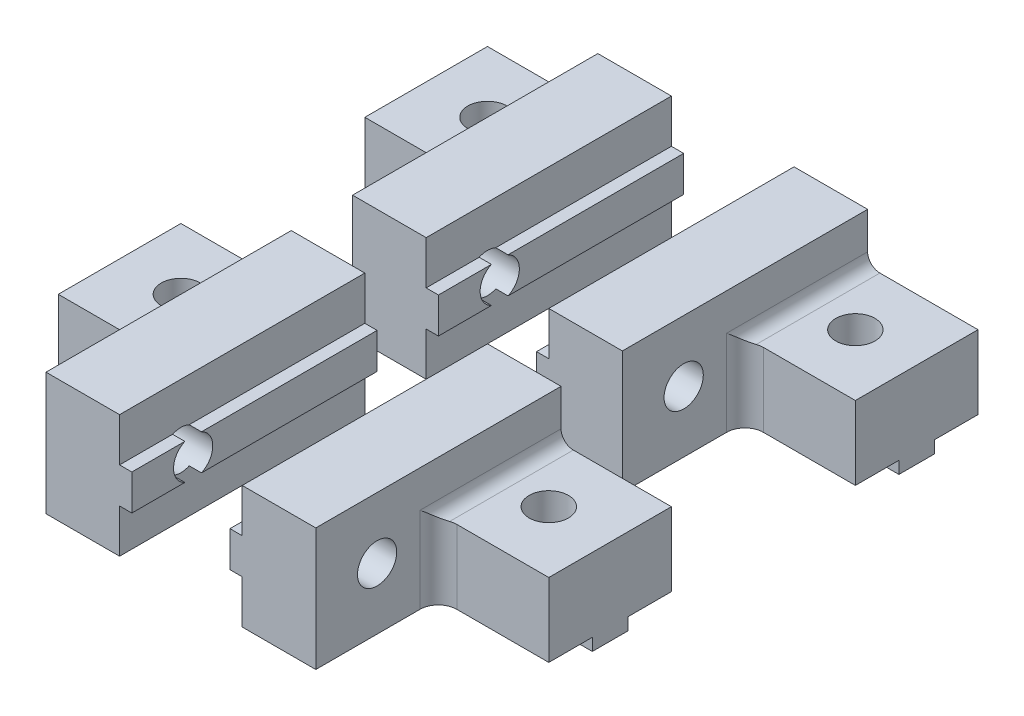
SolidWorks part; units mm, degrees
ref_plane "Front Plane" through (0, 0, 0) normal (0, 0, 1) x (1, 0, 0)
ref_plane "Top Plane" through (0, 0, 0) normal (0, 1, 0) x (1, 0, 0)
ref_plane "Right Plane" through (0, 0, 0) normal (1, 0, 0) x (0, 0, -1)
sketch "Esquisse1" plane through (0, 0, 0) normal (0, 0, 1) x (1, 0, 0)
  line L0 (0, 0) -> (15, 0)
  line L1 (15, 0) -> (15, 6)
  line L2 (15, 6) -> (7, 6)
  line L3 (6, 10) -> (6, 7)
  line L5 (6, 10) -> (0, 10)
  line L6 (0, 10) -> (0, 0)
  arc A0 (7, 6) -> (6, 7) centre (7, 7) cw
  dimension "D1" = 8
  dimension "D2" = 10
  dimension "D3" = 6
  dimension "D4" = 15
extrude "Main" add sketch "Esquisse1" along normal blind 20
sketch "Esquisse4" plane through (0, 0, 0) normal (-1, 0, 0) x (0, 0, 1)
  line L0 (20, 10) -> (0, 10) construction
  line L1 (0, 6.45) -> (20, 6.45)
  line L2 (0, 6.45) -> (0, 3.55)
  line L3 (0, 3.55) -> (20, 3.55)
  line L4 (20, 6.45) -> (20, 3.55)
  line L6 (0, 10) -> (0, 0) construction
  line L7 (20, 10) -> (20, 0) construction
  dimension "D1" = 2.9
  dimension "D2" = 3.55
extrude "VerticalGuidance" add sketch "Esquisse4" along normal blind 1
sketch "Esquisse2" plane through (0, 0, 0) normal (-1, 0, 0) x (0, 0, 1)
  line L0 (20, 10) -> (20, 6.45) construction
  line L5 (20, 0) -> (0, 0) construction
  circle A0 centre (15, 5) radius 1.6
  dimension "D1" = 3.2
  dimension "D2" = 5
  dimension "D3" = 5
extrude "VerticalHole" cut sketch "Esquisse2" against normal through all both and the other way through all
sketch "Esquisse5" plane through (0, 0, 0) normal (0, -1, 0) x (-1, 0, 0)
  line L1 (0, -3.55) -> (-15, -3.55)
  line L2 (0, -3.55) -> (0, -6.45)
  line L3 (0, -6.45) -> (-15, -6.45)
  line L4 (-15, -3.55) -> (-15, -6.45)
  line L8 (0, 0) -> (0, -14.3236) construction
  line L9 (-15, -20) -> (-15, 0) construction
  line L10 (0, 0) -> (-15, 0) construction
  dimension "D1" = 2.9
  dimension "D2" = 3.55
extrude "HorizontalGuidance" add sketch "Esquisse5" along normal blind 1
sketch "Esquisse3" plane through (0, 6, 0) normal (0, -1, 0) x (1, 0, 0)
  line L5 (15, 20) -> (15, 16.249) construction
  line L8 (15, 0) -> (7, 0) construction
  circle A0 centre (10, 5) radius 1.6
  dimension "D1" = 5
  dimension "D2" = 5
  dimension "D3" = 3.2
extrude "HorizontalHole" cut sketch "Esquisse3" against normal through all both and the other way through all
sketch "Esquisse9" plane through (0, 6, 0) normal (0, 1, 0) x (1, 0, 0)
  line L0 (15, -20) -> (15, -16.249) construction
  line L1 (6, -20) -> (15, -20)
  line L2 (6, -20) -> (6, -10)
  line L3 (6, -10) -> (15, -10)
  line L4 (15, -20) -> (15, -10)
  line L5 (15, 0) -> (7, 0) construction
  line L6 (6, -20) -> (6, 0) construction
  dimension "D1" = 10
extrude "Enlèv. mat.-Extru.4" cut sketch "Esquisse9" against normal through all both and the other way through all
fillet "Congé2" radius 1.5 1 edges at (6, 3.5, 10)
ref_plane "SymetryPlan" through (-5, 0, 0) normal (1, 0, 0) x (0, 0, -1)
ref_axis "Axe1" through (-5, 0, -4.75) along (0, 0, 1)
pattern_linear "Répétition linéaire1" count 2 spacing 25 along (0, 0, 1) of bodies 113 114
mirror "Symétrie3" about plane through (-5, 0, 0) normal (1, 0, 0) of bodies 115 113 116 117
